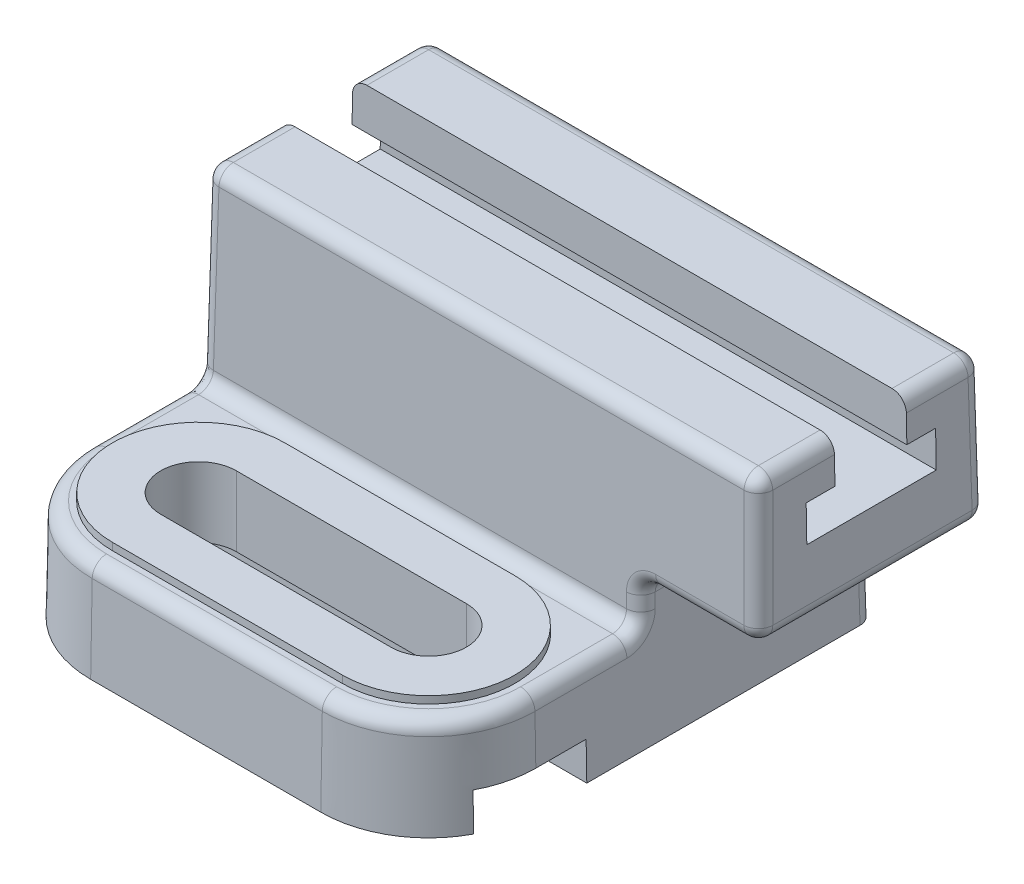
SolidWorks part; units mm, degrees
note: The reader was unsure of these and kept them because the rebuilt part matched: shared geometry of "Sketch2<3>".
ref_plane "Front Plane" through (0, 0, 0) normal (0, 0, 1) x (1, 0, 0)
ref_plane "Top Plane" through (0, 0, 0) normal (0, 1, 0) x (1, 0, 0)
ref_plane "Right Plane" through (0, 0, 0) normal (1, 0, 0) x (0, 0, -1)
sketch "Sketch2" plane through (0, 0, 0) normal (0, 1, 0) x (1, 0, 0)
  line L0 (-25.4, -25.4) -> (25.4, -25.4) construction
  line L1 (49.2125, 49.2125) -> (-49.2125, 49.2125)
  line L2 (49.2125, 49.2125) -> (49.2125, -25.4)
  line L3 (25.4, -49.2125) -> (-25.4, -49.2125)
  line L4 (-49.2125, 49.2125) -> (-49.2125, -25.4)
  line L5 (49.2125, 49.2125) -> (-49.2125, -49.2125) construction
  line L6 (49.2125, -49.2125) -> (-49.2125, 49.2125) construction
  line L7 (-25.4, -6.35) -> (25.4, -6.35)
  line L8 (-25.4, -44.45) -> (25.4, -44.45)
  line L9 (-25.4, -25.4) -> (25.4, -25.4) construction
  line L10 (-25.4, -17.0656) -> (25.4, -17.0656) construction
  line L11 (-25.4, -33.7344) -> (25.4, -33.7344) construction
  arc A0 (49.2125, -25.4) -> (25.4, -49.2125) centre (25.4, -25.4) cw
  arc A1 (-25.4, -49.2125) -> (-49.2125, -25.4) centre (-25.4, -25.4) cw
  arc A4 (-25.4, -6.35) -> (-25.4, -44.45) centre (-25.4, -25.4) ccw
  arc A5 (25.4, -44.45) -> (25.4, -6.35) centre (25.4, -25.4) ccw
  arc A6 (-25.4, -17.0656) -> (-25.4, -33.7344) centre (-25.4, -25.4) ccw construction
  arc A7 (25.4, -33.7344) -> (25.4, -17.0656) centre (25.4, -25.4) ccw construction
  point P0 (0, 0)
  point P18 (0, -25.4)
  point P25 (0, -25.4)
  dimension "D3" = 23.8125
  dimension "D5" = 19.05
  dimension "D6" = 16.6687
  dimension "D1" = 98.425
  dimension "D2" = 98.425
extrude "Boss-Extrude4" add sketch "Sketch2" along normal blind 22.225 draft 1
extrude "Boss-Extrude5" add sketch "Sketch2<3>" along normal blind 1.5875 draft 1 from surface at 22.225 contours L8 A5 L7 A4 A7 L11 A6 L10
sketch "Sketch2<3>" plane through (0, 0, 0) normal (0, 1, 0) x (1, 0, 0) same geometry as "Sketch2"
sketch "Sketch8" plane through (0, 0, 0) normal (0, -1, 0) x (1, 0, 0)
  line L0 (-25.4, 33.7344) -> (25.4, 33.7344) construction
  line L1 (-25.4, 17.0656) -> (25.4, 17.0656) construction
  line L2 (-25.4, 33.7344) -> (25.4, 33.7344)
  line L3 (-25.4, 17.0656) -> (25.4, 17.0656)
  line L4 (-49.2125, 25.4) -> (-49.2125, -49.2125)
  line L5 (-49.2125, -49.2125) -> (49.2125, -49.2125)
  line L6 (49.2125, -49.2125) -> (49.2125, 25.4)
  line L7 (25.4, 49.2125) -> (-25.4, 49.2125)
  line L8 (-49.2125, 25.4) -> (-49.2125, -49.2125)
  line L9 (-49.2125, -49.2125) -> (49.2125, -49.2125)
  line L10 (49.2125, -49.2125) -> (49.2125, 25.4)
  line L11 (25.4, 49.2125) -> (-25.4, 49.2125)
  arc A0 (-25.4, 33.7344) -> (-25.4, 17.0656) centre (-25.4, 25.4) ccw construction
  arc A1 (-25.4, 33.7344) -> (-25.4, 17.0656) centre (-25.4, 25.4) ccw
  arc A2 (-25.4, 49.2125) -> (-49.2125, 25.4) centre (-25.4, 25.4) ccw
  arc A3 (49.2125, 25.4) -> (25.4, 49.2125) centre (25.4, 25.4) ccw
  arc A4 (-25.4, 49.2125) -> (-49.2125, 25.4) centre (-25.4, 25.4) ccw
  arc A5 (49.2125, 25.4) -> (25.4, 49.2125) centre (25.4, 25.4) ccw
  arc A6 (25.4, 17.0656) -> (25.4, 33.7344) centre (25.4, 25.4) ccw construction
  arc A7 (25.4, 17.0656) -> (25.4, 33.7344) centre (25.4, 25.4) ccw
  dimension "D1" = 0
extrude "Cut-Extrude4" cut sketch "Sketch8" against normal through all contours A7 L2 A1 L3
sketch "Sketch3" plane through (0, 22.225, 0) normal (0, 1, 0) x (1, 0, 0)
  line L0 (-48.8246, -1.9754) -> (75.0004, -1.9754)
  line L1 (75.0004, -1.9754) -> (75.0004, 48.8246)
  line L2 (48.8246, 48.8246) -> (48.8246, -25.4) construction
  line L3 (48.8246, 48.8246) -> (48.8246, -1.9754)
  line L4 (48.8246, 48.8246) -> (-48.8246, 48.8246)
  line L5 (-48.8246, 48.8246) -> (-48.8246, -25.4)
  line L6 (-25.4, -48.8246) -> (25.4, -48.8246)
  line L7 (48.8246, -25.4) -> (48.8246, 48.8246)
  line L8 (75.0004, 48.8246) -> (-48.8246, 48.8246)
  line L9 (-48.8246, 48.8246) -> (-48.8246, -1.9754)
  arc A5 (-48.8246, -25.4) -> (-25.4, -48.8246) centre (-25.4, -25.4) ccw
  arc A6 (25.4, -48.8246) -> (48.8246, -25.4) centre (25.4, -25.4) ccw
  dimension "D2" = 50.8
  dimension "D3" = 123.825
  dimension "D1" = 0
extrude "Boss-Extrude6" add sketch "Sketch3" along normal blind 9.525 draft 1
sketch "Sketch5" plane through (0, 31.75, 0) normal (0, 1, 0) x (1, 0, 0)
  line L0 (48.6583, 48.6583) -> (74.6125, 48.6583)
  line L1 (74.6125, 48.6583) -> (74.6125, -1.8092)
  line L2 (74.6125, -1.8092) -> (48.6583, -1.8092)
  line L3 (-49.2125, 49.2125) -> (-49.2125, -25.4) construction
  line L4 (-48.6583, 48.6583) -> (-48.6583, -1.8092)
  line L5 (-48.6583, -1.8092) -> (48.6583, -1.8092)
  line L6 (48.6583, -1.8092) -> (48.6583, 48.6583)
  line L7 (48.6583, 48.6583) -> (-48.6583, 48.6583)
  line L8 (-48.6583, 48.6583) -> (-48.6583, -1.8092)
  line L9 (-48.6583, -1.8092) -> (48.6583, -1.8092)
  line L11 (48.6583, 48.6583) -> (-48.6583, 48.6583)
  dimension "D2" = 123.825
  dimension "D1" = 0
extrude "Boss-Extrude7" add sketch "Sketch5" along normal blind 31.75 draft 1
sketch "Sketch4" plane through (0, 0, 0) normal (0, -1, 0) x (1, 0, 0)
  line L0 (-49.2125, -49.2125) -> (-49.2125, 25.4) construction
  line L1 (-36.5125, -8.3414) -> (36.5125, -8.3414)
  line L2 (-36.5125, -8.3414) -> (-36.5125, -39.2836)
  line L3 (-36.5125, -39.2836) -> (36.5125, -39.2836)
  line L4 (36.5125, -8.3414) -> (36.5125, -39.2836)
  line L5 (-36.5125, -8.3414) -> (36.5125, -39.2836) construction
  line L6 (-36.5125, -39.2836) -> (36.5125, -8.3414) construction
  line L7 (49.2125, -49.2125) -> (49.2125, 25.4) construction
  line L8 (49.2125, -49.2125) -> (-49.2125, -49.2125) construction
  point P0 (0, -23.8125)
  dimension "D1" = 30.9423
  dimension "D2" = 12.7
  dimension "D3" = 12.7
  dimension "D4" = 25.4
extrude "Cut-Extrude1" cut sketch "Sketch4" against normal blind 36.5125 draft 1
sketch "Sketch6" plane through (0, 0, 0) normal (1, 0, 0) x (0, 0, -1)
  line L0 (23.4246, 63.5) -> (23.4246, 46.4344) construction
  line L1 (-1.255, 63.5) -> (48.1041, 63.5) construction
  line L2 (37.7121, 46.4344) -> (9.1371, 46.4344)
  line L3 (9.1371, 46.4344) -> (9.1371, 54.3719)
  line L4 (9.1371, 54.3719) -> (15.4871, 54.3719)
  line L5 (15.4871, 54.3719) -> (15.4871, 63.5)
  line L6 (15.4871, 63.5) -> (31.3621, 63.5)
  line L7 (31.3621, 54.3719) -> (31.3621, 63.5)
  line L8 (37.7121, 54.3719) -> (31.3621, 54.3719)
  line L9 (37.7121, 46.4344) -> (37.7121, 54.3719)
  dimension "D1" = 14.2875
  dimension "D2" = 7.9375
  dimension "D3" = 7.9375
  dimension "D4" = 9.1281
extrude "Cut-Extrude2" cut sketch "Sketch6" against normal through all both and the other way through all
fillet "Fillet1" radius 3.175 30 edges at (-48.6583, 31.75, -48.6583) (41.9637, 22.225, 41.9637) (48.9354, 15.875, -48.9354) (-41.9637, 22.225, 41.9637) (-48.8246, 22.225, 13.6877) (48.8246, 22.225, 13.6877) (0, 22.225, 1.9754) (-48.4643, 42.8625, 1.6152) (48.7414, 26.9875, 1.8923) (48.6583, 31.75, -23.4246) (61.6354, 31.75, 1.8092) (74.6125, 31.75, -23.4246) (74.3354, 47.625, 1.5321) (61.6354, 31.75, -48.6583) (74.3354, 47.625, -48.3812) (12.9771, 63.5, -48.1041) (-48.1041, 63.5, -39.7331) (12.9771, 63.5, 1.255) (74.0583, 63.5, -7.116) (0, 22.225, 48.8246) (35.8752, 36.5125, -23.8125) (36.1938, 18.2562, -8.66) (0, 36.5125, -38.6463) (36.1938, 18.2562, -38.965) (-35.8752, 36.5125, -23.8125) (-36.1938, 18.2562, -38.965) (0, 36.5125, -8.9787) (-36.1938, 18.2562, -8.66) (-48.1041, 63.5, -7.116) (74.0583, 63.5, -39.7331)
sketch "Sketch7" plane through (0, 0, 0) normal (0, -1, 0) x (1, 0, 0)
  line L3 (49.2125, 14.2938) -> (-49.2125, 14.2938)
  line L4 (49.2125, -46.038) -> (49.2125, 25.4) construction
  line L5 (-49.2125, -46.038) -> (-49.2125, 25.4) construction
  line L6 (-49.2125, -46.038) -> (-49.2125, 25.4)
  line L7 (49.2125, -46.038) -> (49.2125, 25.4)
  line L8 (46.4639, 36.5062) -> (-46.4639, 36.5062)
  line L9 (0, 36.5062) -> (0, 14.2938) construction
  arc A1 (-25.4, 49.2125) -> (-49.2125, 25.4) centre (-25.4, 25.4) ccw construction
  arc A2 (49.2125, 25.4) -> (25.4, 49.2125) centre (25.4, 25.4) ccw construction
  arc A3 (-25.4, 49.2125) -> (-49.2125, 25.4) centre (-25.4, 25.4) ccw
  arc A4 (49.2125, 25.4) -> (25.4, 49.2125) centre (25.4, 25.4) ccw
  point P0 (0, 25.4)
  dimension "D2" = 22.2123
extrude "Cut-Extrude3" cut sketch "Sketch7" against normal blind 8.3344
ref_plane "Plane1" through (0, 0, -23.4246) normal (0, 0, 1) x (1, 0, 0)
ref_plane "Plane3" through (0, 0, 25.4) normal (0, 0, 1) x (1, 0, 0)
